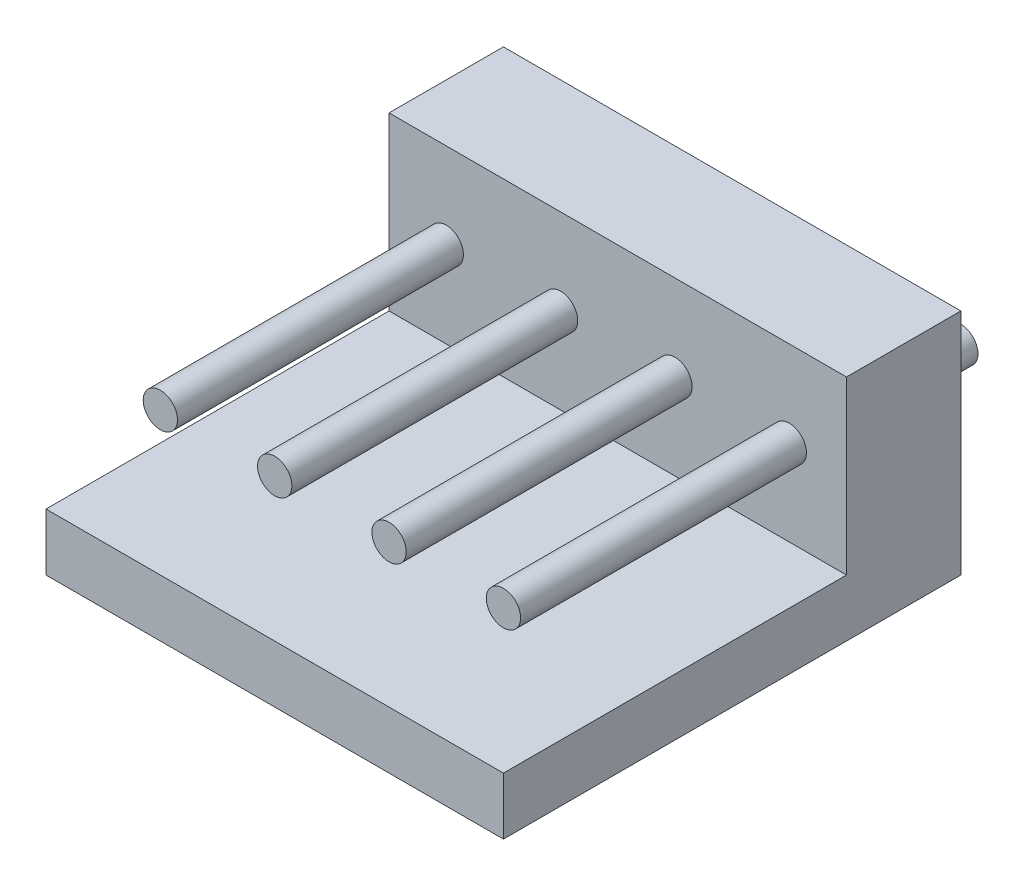
SolidWorks part; units mm, degrees
ref_plane "Спереди" through (0, 0, 0) normal (0, 0, 1) x (1, 0, 0)
ref_plane "Сверху" through (0, 0, 0) normal (0, 1, 0) x (1, 0, 0)
ref_plane "Справа" through (0, 0, 0) normal (1, 0, 0) x (0, 0, -1)
sketch "Эскиз1" plane through (0, 0, 0) normal (0, 0, 1) x (1, 0, 0)
  line L1 (0, 0) -> (20, 0)
  line L2 (0, 0) -> (0, 10)
  line L3 (0, 10) -> (20, 10)
  line L4 (20, 0) -> (20, 10)
  dimension "D1" = 20
  dimension "D2" = 10
extrude "Вытянуть1" add sketch "Эскиз1" along normal blind 5
sketch "Эскиз2" plane through (0, 0, 5) normal (0, 0, 1) x (1, 0, 0)
  line L1 (20, 0) -> (20, 10) construction
  line L2 (0, 0) -> (20, 0)
  line L3 (0, 0) -> (0, 2.5)
  line L4 (0, 2.5) -> (20, 2.5)
  line L7 (20, 0) -> (20, 2.5)
  dimension "D1" = 2.5
extrude "Вытянуть2" add sketch "Эскиз2" along normal blind 15
sketch "Эскиз3" plane through (0, 0, 5) normal (0, 0, 1) x (1, 0, 0)
  line L3 (10, 12.0229) -> (10, -0.8356) construction
  line L4 (0, 10) -> (0, 2.5) construction
  line L5 (20, 2.5) -> (20, 10) construction
  line L7 (10, 6.25) -> (15, 6.25) construction
  line L9 (20, 10) -> (0, 10) construction
  circle A0 centre (12.5, 6.25) radius 0.75
  circle A1 centre (17.5, 6.25) radius 0.75
  circle A2 centre (2.5, 6.25) radius 0.75
  circle A3 centre (7.5, 6.25) radius 0.75
  dimension "D1" = 15
  dimension "D2" = 1.5
  dimension "D3" = 3.75
  dimension "D4" = 5
extrude "Вытянуть3" add sketch "Эскиз3" along normal blind 12.5 and the other way blind 7.5
